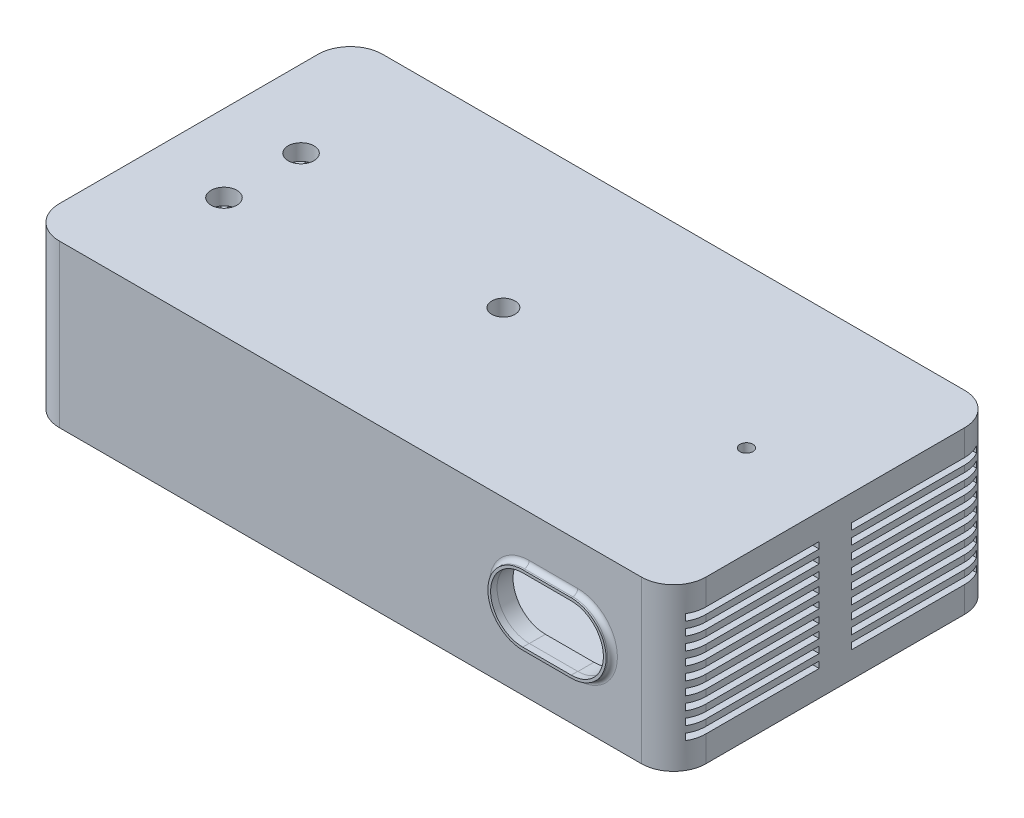
SolidWorks part; units mm, degrees
ref_plane "Front Plane" through (0, 0, 0) normal (0, 0, 1) x (1, 0, 0)
ref_plane "Top Plane" through (0, 0, 0) normal (0, 1, 0) x (1, 0, 0)
ref_plane "Right Plane" through (0, 0, 0) normal (1, 0, 0) x (0, 0, -1)
sketch "Sketch1" plane through (0, 0, 0) normal (0, 1, 0) x (1, 0, 0)
  line L1 (-101.3504, 6.8813) -> (98.6496, 6.8813)
  line L2 (-101.3504, 6.8813) -> (-101.3504, -93.1187)
  line L3 (-101.3504, -93.1187) -> (98.6496, -93.1187)
  line L4 (98.6496, 6.8813) -> (98.6496, -93.1187)
  dimension "D1" = 200
  dimension "D2" = 100
extrude "Boss-Extrude1" add sketch "Sketch1" along normal blind 50
sketch "Sketch2" plane through (0, 50, 0) normal (0, 1, 0) x (1, 0, 0)
  line L0 (98.6496, -93.1187) -> (98.6496, 6.8813) construction
  line L1 (-96.3504, 1.8813) -> (93.6496, 1.8813)
  line L2 (-96.3504, 1.8813) -> (-96.3504, -88.1187)
  line L3 (-96.3504, -88.1187) -> (93.6496, -88.1187)
  line L4 (93.6496, 1.8813) -> (93.6496, -88.1187)
  line L5 (-96.3504, 1.8813) -> (93.6496, -88.1187) construction
  line L6 (-96.3504, -88.1187) -> (93.6496, 1.8813) construction
  line L7 (-101.3504, -93.1187) -> (98.6496, -93.1187) construction
  point P0 (-1.3504, -43.1187)
  dimension "D1" = 190
  dimension "D2" = 5
  dimension "D3" = 5
  dimension "D4" = 90
extrude "Cut-Extrude1" cut sketch "Sketch2" against normal blind 45
sketch "Sketch3" plane through (0, 0, 93.1187) normal (0, 0, 1) x (1, 0, 0)
  line L0 (53.9715, 24.8327) -> (68.9715, 24.8327) construction
  line L1 (53.9715, 34.8327) -> (68.9715, 34.8327)
  line L2 (53.9715, 14.8327) -> (68.9715, 14.8327)
  arc A0 (53.9715, 34.8327) -> (53.9715, 14.8327) centre (53.9715, 24.8327) ccw
  arc A1 (68.9715, 14.8327) -> (68.9715, 34.8327) centre (68.9715, 24.8327) ccw
  point P2 (61.4715, 24.8327)
  dimension "D2" = 15
  dimension "D1" = 20
extrude "Cut-Extrude2" cut sketch "Sketch3" against normal blind 5
sketch "Sketch4" plane through (0, 0, 93.1187) normal (0, 0, 1) x (1, 0, 0)
  line L0 (53.9715, 24.8327) -> (68.9715, 24.8327) construction
  line L7 (53.9715, 35.6094) -> (68.9715, 35.6094)
  line L8 (53.9715, 14.056) -> (68.9715, 14.056)
  arc A4 (53.9715, 35.6094) -> (53.9715, 14.056) centre (53.9715, 24.8327) ccw
  arc A5 (68.9715, 14.056) -> (68.9715, 35.6094) centre (68.9715, 24.8327) ccw
  point P2 (61.4715, 24.8327)
extrude "Boss-Extrude2" add sketch "Sketch4" along normal blind 2
sketch "Sketch5" plane through (0, 0, 95.1187) normal (0, 0, 1) x (1, 0, 0)
  line L0 (53.9715, 24.8327) -> (68.9715, 24.8327) construction
  line L1 (53.9715, 34.7779) -> (68.9715, 34.7779)
  line L2 (53.9715, 14.8876) -> (68.9715, 14.8876)
  arc A0 (53.9715, 34.7779) -> (53.9715, 14.8876) centre (53.9715, 24.8327) ccw
  arc A1 (68.9715, 14.8876) -> (68.9715, 34.7779) centre (68.9715, 24.8327) ccw
  point P2 (61.4715, 24.8327)
extrude "Cut-Extrude3" cut sketch "Sketch5" against normal blind 2
sketch "Sketch18" plane through (0, 0, 0) normal (0, -1, 0) x (1, 0, 0)
  line L0 (-86.3504, 78.1187) -> (-86.3504, 8.1187) construction
  line L1 (-86.3504, 8.1187) -> (83.6496, 8.1187) construction
  line L2 (83.6496, 8.1187) -> (83.6496, 78.1187) construction
  line L3 (83.6496, 78.1187) -> (-83.3317, 78.1187) construction
  line L4 (-83.3317, 78.1187) -> (-77.2942, 59.4025) construction
  line L5 (-101.3504, -6.8813) -> (-101.3504, 93.1187) construction
  line L6 (-101.3504, 93.1187) -> (98.6496, 93.1187) construction
  line L7 (98.6496, 93.1187) -> (98.6496, -6.8813) construction
  line L8 (98.6496, -6.8813) -> (-101.3504, -6.8813) construction
  circle A0 centre (-86.3504, 78.1187) radius 6
  dimension "D5" = 12
  dimension "D1" = 15
  dimension "D2" = 15
  dimension "D3" = 15
  dimension "D4" = 15
extrude "Boss-Extrude3" add sketch "Sketch18" along normal blind 5
sketch "Sketch19" plane through (0, 0, 0) normal (0, -1, 0) x (1, 0, 0)
  line L0 (83.6496, 94.7219) -> (83.6496, 15.0268) construction
  line L1 (83.6496, 15.0268) -> (39.4028, 15.0268) construction
  line L2 (39.4028, 15.0268) -> (39.4028, 78.1187) construction
  line L3 (39.4028, 78.1187) -> (71.4016, 78.1187) construction
  line L4 (-101.3504, 93.1187) -> (98.6496, 93.1187) construction
  line L5 (98.6496, 93.1187) -> (98.6496, -6.8813) construction
  line L6 (-101.3504, 43.1187) -> (98.6496, 43.1187) construction
  line L7 (-101.3504, -6.8813) -> (-101.3504, 93.1187) construction
  line L8 (-1.3504, -6.8813) -> (-1.3504, 93.1187) construction
  line L9 (98.6496, -6.8813) -> (-101.3504, -6.8813) construction
  circle A0 centre (83.6496, 78.1187) radius 6
  circle A1 centre (83.6496, 8.1187) radius 6
  circle A2 centre (-86.3504, 8.1187) radius 6
  dimension "D3" = 12
  dimension "D1" = 15
  dimension "D2" = 15
extrude "Boss-Extrude4" add sketch "Sketch19" along normal blind 5
sketch "Sketch16" plane through (0, 0, 0) normal (0, -1, 0) x (1, 0, 0)
  line L0 (-89.3504, 93.1187) -> (-89.3504, -6.8813) construction
  line L1 (-101.3504, 93.1187) -> (98.6496, 93.1187) construction
  line L2 (98.6496, -6.8813) -> (-101.3504, -6.8813) construction
  line L3 (-89.3504, -6.8813) -> (86.6496, -6.8813) construction
  line L4 (86.6496, -6.8813) -> (86.6496, 81.1187) construction
  line L5 (86.6496, 81.1187) -> (-89.3504, 81.1187) construction
  line L6 (-89.3504, 81.1187) -> (-89.3504, 0) construction
  line L7 (-89.3504, 0) -> (90.9036, 0) construction
  line L8 (98.6496, 93.1187) -> (98.6496, -6.8813) construction
  line L9 (-101.3504, -6.8813) -> (-101.3504, 93.1187) construction
  circle A0 centre (86.6496, 81.1187) radius 4.8859
  dimension "D1" = 12
  dimension "D2" = 12
  dimension "D3" = 12
sketch "Sketch27" plane through (-101.3504, 0, 0) normal (-1, 0, 0) x (0, 0, 1)
  line L0 (43.1187, 50) -> (43.1187, 0) construction
  line L1 (-6.8813, 50) -> (93.1187, 50) construction
  line L2 (-6.8813, 0) -> (81.1187, 0) construction
  line L3 (-6.8813, 25) -> (93.1187, 25) construction
  line L4 (-6.8813, 50) -> (-6.8813, 0) construction
  line L5 (93.1187, 50) -> (93.1187, 0) construction
  line L6 (-6.8813, 50) -> (43.1187, 50) construction
  line L7 (18.1187, 50) -> (18.1187, 0) construction
  line L8 (81.1187, 0) -> (0, 0) construction
  line L9 (-6.8813, 29) -> (43.1187, 29) construction
  line L10 (-6.8813, 33) -> (43.1187, 33) construction
  line L11 (-6.8813, 37) -> (43.1187, 37) construction
  line L12 (-6.8813, 17) -> (43.1187, 17) construction
  line L13 (-6.8813, 21) -> (43.1187, 21) construction
  line L14 (-6.8813, 13) -> (43.1187, 13) construction
  line L15 (-6.8813, 9) -> (43.1187, 9) construction
  line L16 (38.1187, 20) -> (38.1187, 22)
  line L17 (-1.8813, 30) -> (38.1187, 30)
  line L18 (-1.8813, 30) -> (-1.8813, 28)
  line L19 (-1.8813, 28) -> (38.1187, 28)
  line L20 (38.1187, 30) -> (38.1187, 28)
  line L21 (-1.8813, 30) -> (38.1187, 28) construction
  line L22 (-1.8813, 28) -> (38.1187, 30) construction
  line L23 (-1.8813, 34) -> (38.1187, 34)
  line L24 (-1.8813, 34) -> (-1.8813, 32)
  line L25 (-1.8813, 32) -> (38.1187, 32)
  line L26 (38.1187, 34) -> (38.1187, 32)
  line L27 (-1.8813, 34) -> (38.1187, 32) construction
  line L28 (-1.8813, 32) -> (38.1187, 34) construction
  line L29 (-1.8813, 38) -> (38.1187, 38)
  line L30 (-1.8813, 38) -> (-1.8813, 36)
  line L31 (-1.8813, 36) -> (38.1187, 36)
  line L32 (38.1187, 38) -> (38.1187, 36)
  line L33 (-1.8813, 38) -> (38.1187, 36) construction
  line L34 (-1.8813, 36) -> (38.1187, 38) construction
  line L35 (38.1187, 16) -> (38.1187, 18)
  line L36 (-1.8813, 22) -> (38.1187, 22)
  line L37 (-1.8813, 20) -> (-1.8813, 22)
  line L38 (-1.8813, 20) -> (38.1187, 20)
  line L39 (-1.8813, 18) -> (38.1187, 18)
  line L40 (-1.8813, 16) -> (-1.8813, 18)
  line L41 (-1.8813, 16) -> (38.1187, 16)
  line L42 (-1.8813, 12) -> (-1.8813, 14)
  line L43 (38.1187, 12) -> (38.1187, 14)
  line L44 (-1.8813, 14) -> (38.1187, 14)
  line L45 (-1.8813, 12) -> (38.1187, 12)
  point P32 (18.1187, 29)
  point P37 (18.1187, 33)
  point P42 (18.1187, 37)
  dimension "D1" = 4
  dimension "D2" = 4
  dimension "D3" = 4
  dimension "D4" = 4
  dimension "D5" = 4
  dimension "D6" = 4
  dimension "D7" = 4
  dimension "D8" = 40
  dimension "D9" = 40
  dimension "D10" = 40
  dimension "D11" = 2
  dimension "D12" = 2
  dimension "D13" = 2
extrude "Cut-Extrude18" cut sketch "Sketch27" against normal blind 5
sketch "Sketch28" plane through (-101.3504, 0, 0) normal (-1, 0, 0) x (0, 0, 1)
  line L0 (-6.8813, 25) -> (93.1187, 24.8327) construction
  line L1 (-6.8813, 50) -> (-6.8813, 0) construction
  line L2 (93.1187, 14.056) -> (93.1187, 35.6094) construction
  line L3 (43.1187, 50) -> (43.1187, 0) construction
  line L4 (-6.8813, 50) -> (93.1187, 50) construction
  line L5 (-6.8813, 0) -> (81.1187, 0) construction
  line L6 (43.1187, 50) -> (93.1187, 50) construction
  line L7 (93.1187, 50) -> (68.1187, 50) construction
  line L8 (68.1187, 50) -> (68.1187, 0) construction
  line L9 (68.1187, 0) -> (43.1187, 0) construction
  line L10 (43.1187, 0) -> (-6.8813, 0) construction
  line L11 (-6.8813, 0) -> (18.1187, 0) construction
  line L12 (18.1187, 0) -> (18.1187, 50) construction
  line L14 (-1.8813, 26) -> (38.1187, 26)
  line L15 (-1.8813, 26) -> (-1.8813, 24)
  line L16 (-1.8813, 24) -> (38.1187, 24)
  line L17 (38.1187, 26) -> (38.1187, 24)
  line L18 (-1.8813, 26) -> (38.1187, 24) construction
  line L19 (-1.8813, 24) -> (38.1187, 26) construction
  point P12 (18.1187, 25)
  dimension "D1" = 40
  dimension "D2" = 2
extrude "Cut-Extrude19" cut sketch "Sketch28" against normal blind 5
sketch "Sketch29" plane through (-101.3504, 0, 0) normal (-1, 0, 0) x (0, 0, 1)
  line L0 (43.1187, 50) -> (43.1187, 0) construction
  line L1 (-6.8813, 50) -> (93.1187, 50) construction
  line L2 (-6.8813, 0) -> (93.1187, 0) construction
sketch "Sketch30" plane through (-101.3504, 0, 0) normal (-1, 0, 0) x (0, 0, 1)
  line L0 (43.1187, 50) -> (93.1187, 50) construction
  line L1 (-6.8813, 50) -> (93.1187, 50) construction
  line L2 (93.1187, 50) -> (68.1187, 50) construction
  line L3 (68.1187, 50) -> (68.1187, 0) construction
  line L4 (-6.8813, 0) -> (93.1187, 0) construction
  line L5 (68.1187, 0) -> (68.1187, 25) construction
  line L6 (68.1187, 25) -> (43.1187, 25) construction
  line L7 (43.1187, 50) -> (43.1187, 0) construction
  line L8 (43.1187, 25) -> (43.1187, 29) construction
  line L9 (43.1187, 29) -> (68.1187, 29) construction
  line L10 (68.1187, 29) -> (68.1187, 33) construction
  line L11 (68.1187, 33) -> (43.1187, 33) construction
  line L12 (43.1187, 33) -> (43.1187, 37) construction
  line L13 (43.1187, 37) -> (68.1187, 37) construction
  line L14 (68.1187, 37) -> (68.1187, 41) construction
  line L15 (68.1187, 41) -> (43.1187, 41) construction
  line L16 (43.1187, 41) -> (43.1187, 45) construction
  line L17 (43.1187, 45) -> (68.1187, 45) construction
  line L18 (88.1187, 20) -> (88.1187, 22)
  line L19 (48.1187, 26) -> (88.1187, 26)
  line L20 (48.1187, 26) -> (48.1187, 24)
  line L21 (48.1187, 24) -> (88.1187, 24)
  line L22 (88.1187, 26) -> (88.1187, 24)
  line L23 (48.1187, 26) -> (88.1187, 24) construction
  line L24 (48.1187, 24) -> (88.1187, 26) construction
  line L25 (48.1187, 30) -> (88.1187, 30)
  line L26 (48.1187, 30) -> (48.1187, 28)
  line L27 (48.1187, 28) -> (88.1187, 28)
  line L28 (88.1187, 30) -> (88.1187, 28)
  line L29 (48.1187, 30) -> (88.1187, 28) construction
  line L30 (48.1187, 28) -> (88.1187, 30) construction
  line L31 (48.1187, 34) -> (88.1187, 34)
  line L32 (48.1187, 34) -> (48.1187, 32)
  line L33 (48.1187, 32) -> (88.1187, 32)
  line L34 (88.1187, 34) -> (88.1187, 32)
  line L35 (48.1187, 34) -> (88.1187, 32) construction
  line L36 (48.1187, 32) -> (88.1187, 34) construction
  line L37 (48.1187, 38) -> (88.1187, 38)
  line L38 (48.1187, 38) -> (48.1187, 36)
  line L39 (48.1187, 36) -> (88.1187, 36)
  line L40 (88.1187, 38) -> (88.1187, 36)
  line L41 (48.1187, 38) -> (88.1187, 36) construction
  line L42 (48.1187, 36) -> (88.1187, 38) construction
  line L43 (88.1187, 16) -> (88.1187, 18)
  line L44 (88.1187, 12) -> (88.1187, 14)
  line L45 (48.1187, 26) -> (88.1187, 26)
  line L46 (48.1187, 24) -> (88.1187, 24)
  line L47 (48.1187, 22) -> (88.1187, 22)
  line L48 (48.1187, 20) -> (48.1187, 22)
  line L49 (48.1187, 20) -> (88.1187, 20)
  line L50 (48.1187, 18) -> (88.1187, 18)
  line L51 (48.1187, 16) -> (48.1187, 18)
  line L52 (48.1187, 16) -> (88.1187, 16)
  line L53 (48.1187, 14) -> (88.1187, 14)
  line L54 (48.1187, 12) -> (48.1187, 14)
  line L55 (48.1187, 12) -> (88.1187, 12)
  dimension "D1" = 4
  dimension "D2" = 4
  dimension "D3" = 4
  dimension "D4" = 4
  dimension "D5" = 4
  dimension "D6" = 40
  dimension "D7" = 40
  dimension "D8" = 40
  dimension "D9" = 40
  dimension "D10" = 2
  dimension "D11" = 2
  dimension "D12" = 2
  dimension "D13" = 2
extrude "Cut-Extrude20" cut sketch "Sketch30" against normal blind 5 contours L48 L49 L18 L47 | L51 L52 L43 L50 | L54 L55 L44 L53 | L34 L31 L32 L33 | L40 L37 L38 L39 | L28 L25 L26 L27 | L22 L19 L20 L21 region at (-101.3504, 21, 68.1187) region at (-101.3504, 25, 68.1187) region at (-101.3504, 29, 68.1187) region at (-101.3504, 33, 68.1187) region at (-101.3504, 37, 68.1187) region at (-101.3504, 17, 68.1187) region at (-101.3504, 13, 68.1187)
sketch "Sketch31" plane through (98.6496, 0, 0) normal (1, 0, 0) x (0, 0, -1)
  line L0 (-43.1187, 50) -> (-43.1187, 0) construction
  line L1 (-43.1187, 0) -> (-93.1187, 0) construction
  line L2 (-93.1187, 0) -> (-93.1187, 25) construction
  line L3 (-93.1187, 50) -> (-93.1187, 0) construction
  line L4 (-93.1187, 25) -> (-43.1187, 25) construction
  line L5 (-43.1187, 25) -> (-43.1187, 29) construction
  line L6 (-43.1187, 29) -> (-93.1187, 29) construction
  line L7 (-93.1187, 29) -> (-93.1187, 33) construction
  line L8 (-93.1187, 33) -> (-43.1187, 33) construction
  line L9 (-43.1187, 33) -> (-43.1187, 37) construction
  line L10 (-43.1187, 37) -> (-93.1187, 37) construction
  line L11 (-93.1187, 37) -> (-93.1187, 41) construction
  line L12 (-93.1187, 41) -> (-43.1187, 41) construction
  line L13 (-43.1187, 0) -> (-93.1187, 0) construction
  line L14 (-93.1187, 0) -> (-68.1187, 0) construction
  line L15 (-68.1187, 0) -> (-68.1187, 50) construction
  line L16 (-93.1187, 50) -> (6.8813, 50) construction
  line L17 (-88.1187, 26) -> (-48.1187, 26)
  line L19 (-88.1187, 26) -> (-88.1187, 24)
  line L20 (-88.1187, 24) -> (-48.1187, 24)
  line L21 (-48.1187, 26) -> (-48.1187, 24)
  line L22 (-88.1187, 26) -> (-48.1187, 24) construction
  line L23 (-88.1187, 24) -> (-48.1187, 26) construction
  line L24 (-88.1187, 30) -> (-48.1187, 30)
  line L25 (-88.1187, 30) -> (-88.1187, 28)
  line L26 (-88.1187, 28) -> (-48.1187, 28)
  line L27 (-48.1187, 30) -> (-48.1187, 28)
  line L28 (-88.1187, 30) -> (-48.1187, 28) construction
  line L29 (-88.1187, 28) -> (-48.1187, 30) construction
  line L30 (-88.1187, 34) -> (-48.1187, 34)
  line L31 (-88.1187, 34) -> (-88.1187, 32)
  line L32 (-88.1187, 32) -> (-48.1187, 32)
  line L33 (-48.1187, 34) -> (-48.1187, 32)
  line L34 (-88.1187, 34) -> (-48.1187, 32) construction
  line L35 (-88.1187, 32) -> (-48.1187, 34) construction
  line L36 (-88.1187, 38) -> (-48.1187, 38)
  line L37 (-88.1187, 38) -> (-88.1187, 36)
  line L38 (-88.1187, 36) -> (-48.1187, 36)
  line L39 (-48.1187, 38) -> (-48.1187, 36)
  line L40 (-88.1187, 38) -> (-48.1187, 36) construction
  line L41 (-88.1187, 36) -> (-48.1187, 38) construction
  line L42 (-88.1187, 42) -> (-48.1187, 42)
  line L43 (-88.1187, 42) -> (-88.1187, 40)
  line L44 (-88.1187, 40) -> (-48.1187, 40)
  line L45 (-48.1187, 42) -> (-48.1187, 40)
  line L46 (-88.1187, 42) -> (-48.1187, 40) construction
  line L47 (-88.1187, 40) -> (-48.1187, 42) construction
  line L49 (-48.1187, 20) -> (-48.1187, 22)
  line L50 (-88.1187, 22) -> (-48.1187, 22)
  line L51 (-88.1187, 20) -> (-48.1187, 20)
  line L52 (-88.1187, 20) -> (-88.1187, 22)
  line L53 (-88.1187, 16) -> (-88.1187, 18)
  line L54 (-88.1187, 18) -> (-48.1187, 18)
  line L55 (-48.1187, 16) -> (-48.1187, 18)
  line L56 (-88.1187, 16) -> (-48.1187, 16)
  line L57 (-48.1187, 12) -> (-48.1187, 14)
  line L58 (-88.1187, 14) -> (-48.1187, 14)
  line L59 (-88.1187, 12) -> (-48.1187, 12)
  line L60 (-88.1187, 12) -> (-88.1187, 14)
  line L61 (-88.1187, 8) -> (-88.1187, 10)
  line L62 (-48.1187, 8) -> (-48.1187, 10)
  line L63 (-88.1187, 10) -> (-48.1187, 10)
  line L64 (-88.1187, 8) -> (-48.1187, 8)
  point P4 (-68.1187, 25)
  point P27 (-68.1187, 29)
  point P32 (-68.1187, 33)
  point P37 (-68.1187, 37)
  point P42 (-68.1187, 41)
  dimension "D1" = 4
  dimension "D2" = 4
  dimension "D3" = 4
  dimension "D4" = 4
  dimension "D5" = 40
  dimension "D6" = 40
  dimension "D7" = 40
  dimension "D8" = 40
  dimension "D9" = 40
  dimension "D10" = 2
  dimension "D11" = 2
  dimension "D12" = 2
  dimension "D13" = 2
  dimension "D14" = 2
extrude "Cut-Extrude21" cut sketch "Sketch31" against normal blind 5
sketch "Sketch32" plane through (98.6496, 0, 0) normal (1, 0, 0) x (0, 0, -1)
  line L0 (-43.1187, 50) -> (6.8813, 50) construction
  line L1 (6.8813, 50) -> (-18.1187, 50) construction
  line L2 (-18.1187, 50) -> (-18.1187, 0) construction
  line L3 (-93.1187, 0) -> (6.8813, 0) construction
  line L4 (-18.1187, 0) -> (-18.1187, 25) construction
  line L5 (-18.1187, 25) -> (6.8813, 25) construction
  line L6 (6.8813, 50) -> (6.8813, 0) construction
  line L7 (6.8813, 25) -> (6.8813, 29) construction
  line L8 (6.8813, 29) -> (-18.1187, 29) construction
  line L9 (-18.1187, 29) -> (-18.1187, 33) construction
  line L10 (-18.1187, 33) -> (6.8813, 33) construction
  line L11 (6.8813, 33) -> (6.8813, 37) construction
  line L12 (6.8813, 37) -> (-18.1187, 37) construction
  line L13 (-18.1187, 37) -> (-18.1187, 41) construction
  line L14 (-18.1187, 41) -> (6.8813, 41) construction
  line L16 (-38.1187, 26) -> (1.8813, 26)
  line L17 (-38.1187, 26) -> (-38.1187, 24)
  line L18 (-38.1187, 24) -> (1.8813, 24)
  line L19 (1.8813, 26) -> (1.8813, 24)
  line L20 (-38.1187, 26) -> (1.8813, 24) construction
  line L21 (-38.1187, 24) -> (1.8813, 26) construction
  line L22 (-38.1187, 30) -> (1.8813, 30)
  line L23 (-38.1187, 30) -> (-38.1187, 28)
  line L24 (-38.1187, 28) -> (1.8813, 28)
  line L25 (1.8813, 30) -> (1.8813, 28)
  line L26 (-38.1187, 30) -> (1.8813, 28) construction
  line L27 (-38.1187, 28) -> (1.8813, 30) construction
  line L28 (-38.1187, 34) -> (1.8813, 34)
  line L29 (-38.1187, 34) -> (-38.1187, 32)
  line L30 (-38.1187, 32) -> (1.8813, 32)
  line L31 (1.8813, 34) -> (1.8813, 32)
  line L32 (-38.1187, 34) -> (1.8813, 32) construction
  line L33 (-38.1187, 32) -> (1.8813, 34) construction
  line L34 (-38.1187, 38) -> (1.8813, 38)
  line L35 (-38.1187, 38) -> (-38.1187, 36)
  line L36 (-38.1187, 36) -> (1.8813, 36)
  line L37 (1.8813, 38) -> (1.8813, 36)
  line L38 (-38.1187, 38) -> (1.8813, 36) construction
  line L39 (-38.1187, 36) -> (1.8813, 38) construction
  line L40 (-38.1187, 42) -> (1.8813, 42)
  line L41 (-38.1187, 42) -> (-38.1187, 40)
  line L42 (-38.1187, 40) -> (1.8813, 40)
  line L43 (1.8813, 42) -> (1.8813, 40)
  line L44 (-38.1187, 42) -> (1.8813, 40) construction
  line L45 (-38.1187, 40) -> (1.8813, 42) construction
  line L46 (-38.1187, 20) -> (-38.1187, 22)
  line L47 (-38.1187, 22) -> (1.8813, 22)
  line L48 (1.8813, 20) -> (1.8813, 22)
  line L49 (-38.1187, 20) -> (1.8813, 20)
  line L50 (1.8813, 16) -> (1.8813, 18)
  line L51 (-38.1187, 18) -> (1.8813, 18)
  line L52 (-38.1187, 16) -> (-38.1187, 18)
  line L53 (-38.1187, 16) -> (1.8813, 16)
  line L54 (-38.1187, 12) -> (-38.1187, 14)
  line L55 (1.8813, 12) -> (1.8813, 14)
  line L56 (-38.1187, 14) -> (1.8813, 14)
  line L57 (-38.1187, 12) -> (1.8813, 12)
  line L58 (1.8813, 8) -> (1.8813, 10)
  line L59 (-38.1187, 10) -> (1.8813, 10)
  line L60 (-38.1187, 8) -> (-38.1187, 10)
  line L61 (-38.1187, 8) -> (1.8813, 8)
  dimension "D1" = 4
  dimension "D2" = 4
  dimension "D3" = 4
  dimension "D4" = 4
  dimension "D5" = 40
  dimension "D6" = 40
  dimension "D7" = 40
  dimension "D8" = 40
  dimension "D9" = 40
  dimension "D10" = 2
  dimension "D11" = 2
  dimension "D12" = 2
  dimension "D13" = 2
  dimension "D14" = 2
extrude "Cut-Extrude22" cut sketch "Sketch32" against normal blind 5
fillet "Fillet1" radius 10 4 edges at (-101.3504, 25, -6.8813) (-101.3504, 25, 93.1187) (98.6496, 25, -6.8813) (98.6496, 25, 93.1187)
fillet "Fillet3" radius 2 8 edges at (-86.3504, -5, 2.1187) (83.6496, 0, 14.1187) (83.6496, -5, 14.1187) (-86.3504, 0, 14.1187) (83.6496, 0, 84.1187) (83.6496, -5, 72.1187) (-86.3504, 0, 84.1187) (-86.3504, -5, 72.1187)
fillet "Fillet4" radius 1.5 4 edges at (79.7482, 24.8327, 93.1187) (61.4715, 14.056, 93.1187) (43.1948, 24.8327, 93.1187) (61.4715, 35.6094, 93.1187)
sketch "Sketch33" plane through (0, 5, 0) normal (0, 1, 0) x (1, 0, 0)
  line L0 (-96.3504, 1.8813) -> (93.6496, 1.8813) construction
  line L1 (93.6496, 1.8813) -> (93.6496, -88.1187) construction
  line L2 (93.6496, -88.1187) -> (-96.3504, -88.1187) construction
  line L3 (-96.3504, -88.1187) -> (-96.3504, 1.8813) construction
  line L4 (-96.3504, 1.8813) -> (-1.3504, 1.8813) construction
  line L5 (-1.3504, 1.8813) -> (-1.3504, -88.1187) construction
  line L6 (-1.3504, -88.1187) -> (-96.3504, -88.1187) construction
  line L7 (-96.3504, -88.1187) -> (-48.8504, -88.1187) construction
  line L8 (-48.8504, -88.1187) -> (-48.8504, 1.8813) construction
  line L9 (-48.8504, 1.8813) -> (-48.8504, -43.1187) construction
  line L10 (-48.8504, -43.1187) -> (-48.8504, -20.6187) construction
  line L11 (-48.8504, -20.6187) -> (-96.3504, -20.6187) construction
  line L12 (-96.3504, -20.6187) -> (-72.6004, -20.6187) construction
  line L13 (-72.6004, -20.6187) -> (-72.6004, -88.1187) construction
  line L14 (-72.6004, -88.1187) -> (-48.8504, -43.1187) construction
  line L15 (-48.8504, -43.1187) -> (84.0804, -43.1187) construction
  circle A0 centre (-72.6004, -20.6187) radius 3.2743
  circle A1 centre (69.8996, -20.6187) radius 3.2743
  circle A2 centre (69.8996, -65.6187) radius 3.2743
  circle A3 centre (-72.6004, -65.6187) radius 3.2743
extrude "Boss-Extrude5" add sketch "Sketch33" along normal blind 10
sketch "Sketch34" plane through (0, 15, 0) normal (0, 1, 0) x (1, 0, 0)
  circle A0 centre (-72.6004, -20.6187) radius 2.1387
extrude "Cut-Extrude23" cut sketch "Sketch34" against normal blind 8
sketch "Sketch35" plane through (0, 15, 0) normal (0, 1, 0) x (1, 0, 0)
  circle A0 centre (69.8996, -20.6187) radius 2.3578
extrude "Cut-Extrude24" cut sketch "Sketch35" against normal blind 8
sketch "Sketch36" plane through (0, 15, 0) normal (0, 1, 0) x (1, 0, 0)
  circle A0 centre (69.9839, -65.6946) radius 2.2997
  circle A1 centre (-72.6004, -65.6187) radius 2.067
extrude "Cut-Extrude25" cut sketch "Sketch36" against normal blind 8
sketch "Sketch37" plane through (0, 50, 0) normal (0, 1, 0) x (1, 0, 0)
  line L1 (-96.3504, 1.8813) -> (93.6496, 1.8813)
  line L2 (-96.3504, 1.8813) -> (-96.3504, -88.1187)
  line L3 (-96.3504, -88.1187) -> (93.6496, -88.1187)
  line L4 (93.6496, 1.8813) -> (93.6496, -88.1187)
extrude "Boss-Extrude6" add sketch "Sketch37" against normal blind 5
sketch "Sketch38" plane through (0, 50, 0) normal (0, 1, 0) x (1, 0, 0)
  circle A0 centre (-77.4699, -32.2483) radius 4
  circle A1 centre (-77.4699, -56.0683) radius 4
  circle A2 centre (70.3349, -42.2977) radius 2
  circle A3 centre (-4.8285, -42.2977) radius 3.5971
  dimension "D1" = 8
  dimension "D2" = 8
  dimension "D3" = 7.1941
  dimension "D4" = 4
extrude "Cut-Extrude26" cut sketch "Sketch38" against normal blind 15
